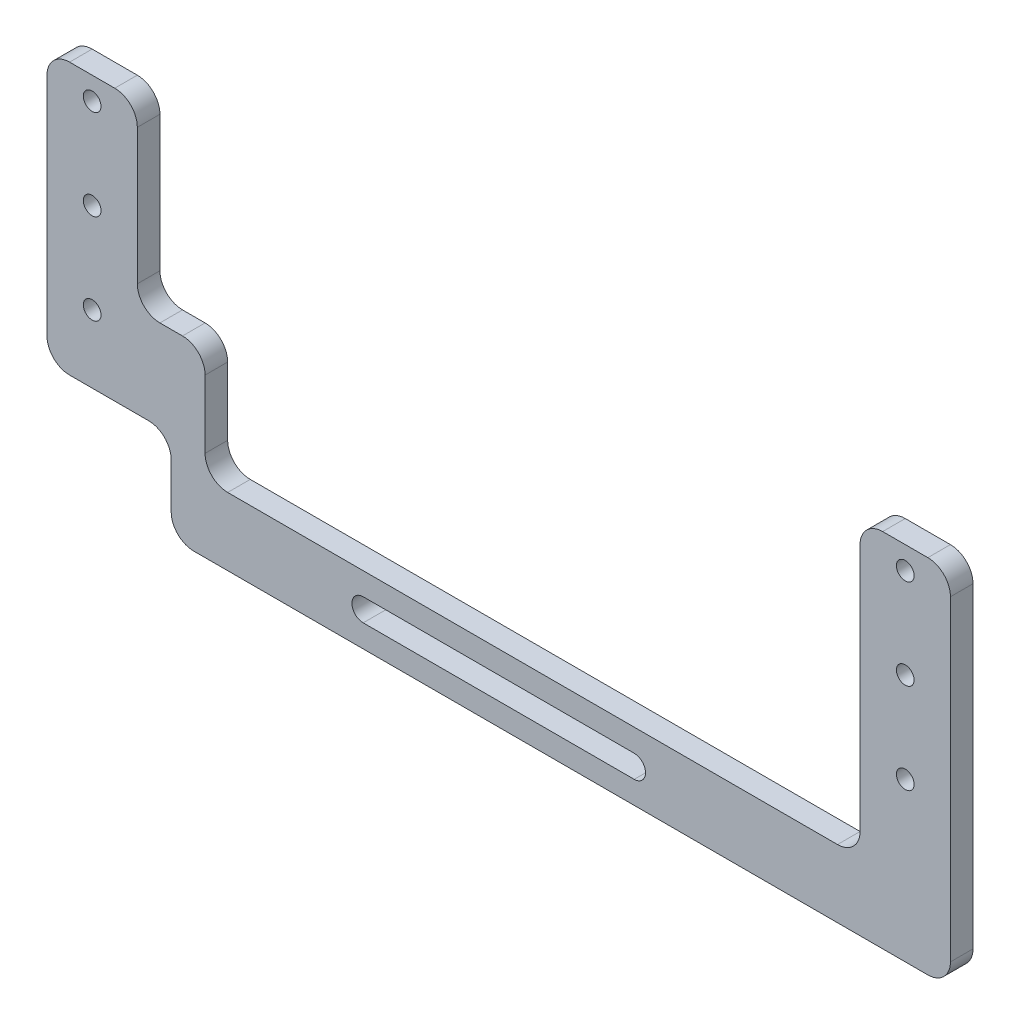
SolidWorks part; units mm, degrees
material "PC High Viscosity"
ref_plane "Front Plane" through (0, 0, 0) normal (0, 0, 1) x (1, 0, 0)
ref_plane "Top Plane" through (0, 0, 0) normal (0, 1, 0) x (1, 0, 0)
ref_plane "Right Plane" through (0, 0, 0) normal (1, 0, 0) x (0, 0, -1)
sketch "Sketch1" plane through (0, 0, 0) normal (0, 0, 1) x (1, 0, 0)
  line L13 (51.9148, 0) -> (77.3148, 0)
  line L14 (77.3148, 0) -> (77.3148, -101.6)
  line L15 (77.3148, -101.6) -> (-141.7602, -101.6)
  line L17 (51.9148, -101.6) -> (77.3148, -101.6)
  line L26 (-151.2852, -50.8) -> (-151.2852, 0)
  line L27 (-151.2852, 0) -> (-176.6852, 0)
  line L28 (-87.7852, -92.075) -> (-11.5852, -92.075) construction
  line L29 (-87.7852, -88.9) -> (-11.5852, -88.9)
  line L30 (-87.7852, -95.25) -> (-11.5852, -95.25)
  line L31 (-141.7602, -101.6) -> (77.3148, -101.6) construction
  line L33 (51.9148, -82.55) -> (51.9148, 0)
  line L35 (77.3148, 0) -> (-176.6852, 0) construction
  line L36 (-132.2352, -82.55) -> (-132.2352, -50.8)
  line L37 (-132.2352, -50.8) -> (-151.2852, -50.8)
  line L38 (-141.7602, -101.6) -> (-141.7602, -76.2)
  line L39 (-141.7602, -76.2) -> (-176.6852, -76.2)
  line L40 (-132.2352, -82.55) -> (51.9148, -82.55)
  line L41 (-176.6852, -76.2) -> (-176.6852, 0)
  line L43 (-151.2852, -337.8318) -> (-151.2852, 259.0682) construction
  arc A0 (-87.7852, -88.9) -> (-87.7852, -95.25) centre (-87.7852, -92.075) ccw
  arc A1 (-11.5852, -95.25) -> (-11.5852, -88.9) centre (-11.5852, -92.075) ccw
  point P1 (-49.6852, -92.075)
  dimension "D4" = 3.175
  dimension "D1" = 25.4
  dimension "D2" = 9.525
  dimension "D3" = 101.6
  dimension "D5" = 203.2
  dimension "D6" = 19.05
  dimension "D7" = 25.4
  dimension "D8" = 76.2
  dimension "D9" = 25.4
  dimension "D10" = 50.8
  dimension "D11" = 76.2
  dimension "D12" = 9.525
  dimension "D14" = 9.525
  dimension "D15" = 127
extrude "Boss-Extrude2" add sketch "Sketch1" along normal blind 6.35 contours L41 L39 L38 L15 L14 L13 L33 L40 L36 L37 L26 L27 A1 L30 A0 L29 region at (64.6148, -2.7357, 0)
fillet "Fillet1" radius 6.35 12 edges at (-176.6852, 0, 3.175) (-151.2852, 0, 3.175) (-151.2852, -50.8, 3.175) (-132.2352, -50.8, 3.175) (-132.2352, -82.55, 3.175) (51.9148, 0, 3.175) (77.3148, 0, 3.175) (-141.7602, -101.6, 3.175) (-141.7602, -76.2, 3.175) (-176.6852, -76.2, 3.175) (51.9148, -82.55, 3.175) (77.3148, -101.6, 3.175)
sketch "Sketch2" plane through (0, 0, 6.35) normal (0, 0, 1) x (1, 0, 0)
  line L0 (58.2648, 0) -> (70.9648, 0) construction
  line L1 (-157.6352, 0) -> (-170.3352, 0) construction
  circle A0 centre (64.6148, -6.35) radius 2.4892
  circle A1 centre (64.6148, -31.75) radius 2.4892
  circle A2 centre (64.6148, -57.15) radius 2.4892
  circle A3 centre (-163.9852, -6.35) radius 2.4892
  circle A4 centre (-163.9852, -31.75) radius 2.4892
  circle A5 centre (-163.9852, -57.15) radius 2.4892
  point P9 (64.6148, 0)
  point P14 (-163.9852, 0)
  dimension "D1" = 4.9784
  dimension "D5" = 4.9784
  dimension "D3" = 6.35
  dimension "D4" = 25.4
  dimension "D6" = 6.35
  dimension "D8" = 25.4
  dimension "D2" = 3
  dimension "D7" = 3
extrude "Cut-Extrude1" cut sketch "Sketch2" against normal through all
